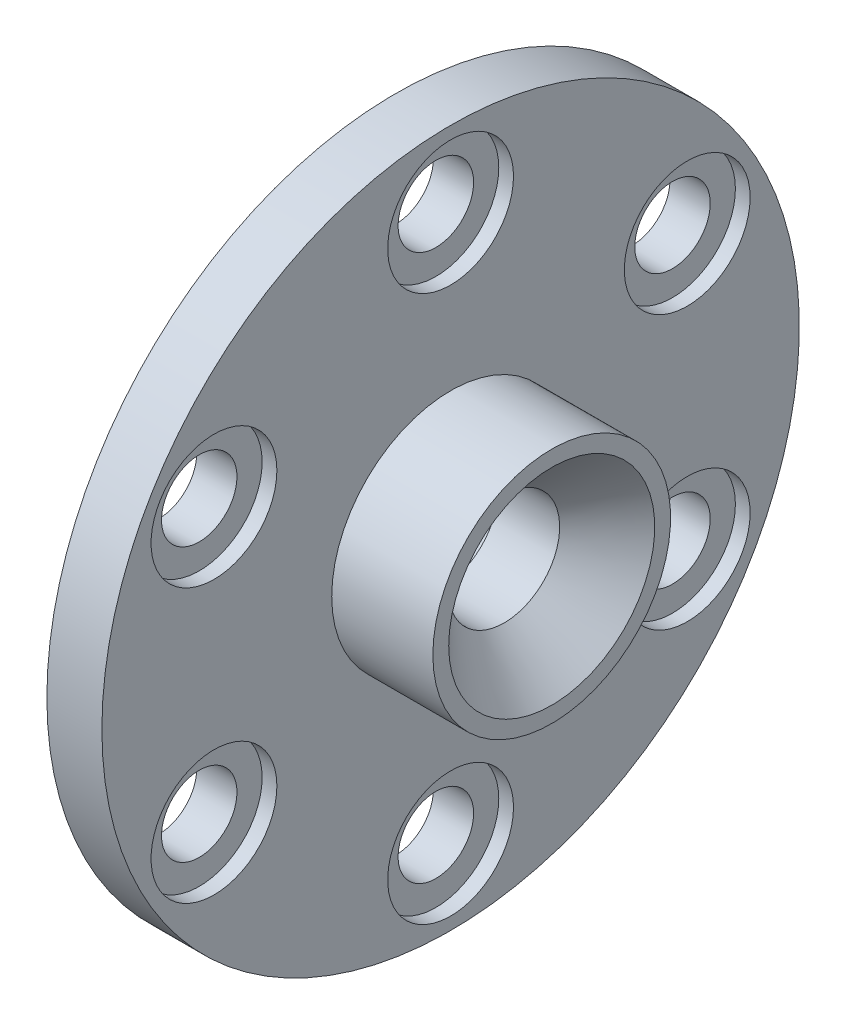
SolidWorks part; units mm, degrees
ref_plane "Front Plane" through (0, 0, 0) normal (0, 0, 1) x (1, 0, 0)
ref_plane "Top Plane" through (0, 0, 0) normal (0, 1, 0) x (1, 0, 0)
ref_plane "Right Plane" through (0, 0, 0) normal (1, 0, 0) x (0, 0, -1)
sketch "Sketch2" plane through (0, 0, 0) normal (0, 0, 1) x (1, 0, 0)
  line L0 (0, 0) -> (58.591, 0) construction
  line L2 (0, 0) -> (18.4, 0)
  line L3 (0, 0) -> (0, 2.5)
  line L4 (0, 2.5) -> (18.4, 2.5)
  line L5 (18.4, 0) -> (18.4, 2.5)
  line L6 (6, 2.5) -> (6, 6)
  line L11 (6, 6) -> (9.97, 6)
  line L16 (12.97, 6) -> (12.97, 3)
  line L17 (12.97, 3) -> (13.6304, 3)
  line L18 (13.6304, 3) -> (13.6304, 2.5)
  line L19 (13.6304, 2.5) -> (6, 2.5)
  line L22 (13.6304, 2.5) -> (16.1104, 2.5)
  line L23 (13.6304, 2.5) -> (13.6304, 4)
  line L24 (13.6304, 4) -> (16.1104, 4)
  line L25 (16.1104, 2.5) -> (16.1104, 4)
  line L27 (6, 6) -> (9.97, 6)
  line L28 (6, 6) -> (6, 9)
  line L29 (6, 9) -> (9.97, 9)
  line L30 (9.97, 6) -> (9.97, 9)
  line L31 (6, 9) -> (6, 8.25)
  line L32 (6, 8.25) -> (5, 8.25)
  line L33 (8.58, 22.001) -> (8.58, 12.476) construction
  line L34 (5, 12.476) -> (12.16, 12.476)
  line L35 (9.97, 9) -> (12.16, 9)
  line L36 (5, 7.5) -> (3, 7.5)
  line L37 (5, 8.25) -> (5, 12.476)
  line L38 (5, 7.5) -> (5, 14)
  line L39 (5, 14) -> (3, 14)
  line L40 (3, 7.5) -> (3, 14)
  line L41 (5, 22.001) -> (12.16, 22.001)
  line L42 (5, 22.001) -> (5, 30.1625)
  line L43 (5, 30.1625) -> (12.16, 30.1625)
  line L44 (12.16, 22.001) -> (12.16, 30.1625)
  line L49 (16.6304, 22.001) -> (16.6304, 7.5)
  line L51 (23.0104, 7.5) -> (23.0104, 6.5)
  line L54 (16.1104, 4) -> (13.6304, 4)
  line L56 (18.0304, 7.5) -> (23.0104, 7.5)
  line L57 (13.16, 22.001) -> (16.6304, 22.001)
  line L58 (16.1104, 3.5) -> (20.0104, 3.5)
  line L59 (29.9004, 14) -> (26.9004, 11)
  line L60 (4, 31.75) -> (18.0304, 31.75)
  line L61 (18.0304, 7.5) -> (23.0104, 7.5)
  line L62 (18.0304, 7.5) -> (18.0304, 12)
  line L63 (18.0304, 12) -> (23.0104, 12)
  line L64 (23.0104, 7.5) -> (23.0104, 12)
  line L65 (18.0304, 31.75) -> (18.0304, 12)
  line L66 (23.0104, 11) -> (26.9004, 11)
  line L67 (34.8004, 23) -> (31.3004, 19.5)
  line L68 (35.8004, 31) -> (38.7904, 33.99)
  line L69 (29.9004, 14) -> (29.9004, 15)
  line L70 (29.9004, 15) -> (22.9304, 15)
  line L71 (22.9304, 15) -> (21.0304, 15)
  line L72 (18.0304, 7.5) -> (16.6304, 7.5)
  line L73 (21.0304, 15) -> (21.0304, 43)
  line L74 (20.0304, 40) -> (10.0704, 40)
  line L75 (10.0704, 40) -> (4, 40)
  line L76 (21.0304, 43) -> (20.0304, 43)
  line L77 (22.9304, 15) -> (29.9004, 15)
  line L78 (22.9304, 15) -> (22.9304, 21)
  line L79 (22.9304, 21) -> (29.9004, 21)
  line L80 (29.9004, 15) -> (29.9004, 21)
  line L81 (10.0704, 40) -> (20.0304, 40)
  line L82 (10.0704, 40) -> (10.0704, 50)
  line L83 (10.0704, 50) -> (20.0304, 50)
  line L84 (20.0304, 40) -> (20.0304, 50)
  line L85 (4, 40) -> (4, 31.75)
  line L86 (12.97, 3) -> (12.97, 2.5)
  line L87 (31.3004, 19.5) -> (29.9004, 19.5)
  line L88 (21.51, 63.5) -> (21.51, 44)
  line L89 (21.51, 63.5) -> (25.9304, 63.5)
  line L90 (25.9304, 63.5) -> (25.9304, 25)
  line L91 (27.8304, 25) -> (25.9304, 25)
  line L92 (10.0704, 48) -> (9, 48)
  line L93 (9, 48) -> (9, 53.476)
  line L94 (9, 53.476) -> (20.0304, 53.476)
  line L95 (20.0304, 53.476) -> (20.0304, 50)
  line L96 (14.5152, 63.001) -> (14.5152, 53.476) construction
  line L97 (9, 63.001) -> (20.0304, 63.001)
  line L98 (9, 63.001) -> (9, 68.2625)
  line L99 (9, 68.2625) -> (20.0304, 68.2625)
  line L100 (20.0304, 63.001) -> (20.0304, 68.2625)
  line L101 (12.97, 6) -> (11.97, 6)
  line L102 (9, 42.5) -> (5, 42.5)
  line L103 (9, 42.5) -> (9, 55)
  line L104 (9, 55) -> (5, 55)
  line L105 (5, 42.5) -> (5, 55)
  line L106 (9.97, 6) -> (10.87, 6)
  line L107 (27.8304, 25) -> (34.8004, 25)
  line L108 (34.8004, 25) -> (34.8004, 23)
  line L109 (0, 0) -> (-2, 0)
  line L110 (0, 0) -> (0, 11)
  line L111 (27.8304, 25) -> (34.8004, 25)
  line L112 (27.8304, 25) -> (27.8304, 32.5)
  line L113 (27.8304, 32.5) -> (34.8004, 32.5)
  line L114 (34.8004, 25) -> (34.8004, 32.5)
  line L115 (35.8004, 31) -> (34.8004, 31)
  line L116 (27.8304, 32.5) -> (27.8304, 64.5)
  line L117 (21.1827, 74.025) -> (6.8477, 74.025)
  line L118 (6.8477, 74.025) -> (6.8477, 76.2)
  line L119 (38.7904, 47.29) -> (30.8304, 55.25)
  line L120 (0, 11) -> (-2, 11)
  line L121 (38.7904, 43.815) -> (30.8529, 43.815)
  line L123 (-4.8, 69.85) -> (1.55, 76.2)
  line L124 (38.7904, 47.29) -> (38.7904, 33.99)
  line L125 (-2, 0) -> (-2, 11)
  line L126 (38.7904, 37.465) -> (30.8529, 37.465)
  line L127 (30.8529, 43.815) -> (30.8529, 37.465)
  line L128 (6, 2.5) -> (6, 0)
  line L129 (0, 63.5) -> (0, 30)
  line L132 (5, 63.5) -> (0, 63.5)
  line L136 (-1.8, 30) -> (-11.76, 30)
  line L138 (-13.76, 25.4) -> (-2, 25.4)
  line L139 (-2, 25.4) -> (-2, 11.5)
  line L140 (27.8304, 64.5) -> (21.1827, 64.5)
  line L141 (-1.8, 30) -> (-11.76, 30)
  line L142 (-1.8, 30) -> (-1.8, 39)
  line L143 (-1.8, 39) -> (-11.76, 39)
  line L144 (-11.76, 30) -> (-11.76, 39)
  line L145 (21.1827, 64.5) -> (21.1827, 74.025)
  line L146 (-12.76, 37) -> (-12.76, 47.29)
  line L147 (-12.76, 37) -> (-11.76, 37)
  line L148 (30.8304, 55.25) -> (30.8304, 76.2)
  line L149 (11.97, 6) -> (11.97, 5.45)
  line L154 (-2, 11.5) -> (1, 11.5)
  line L155 (5, 60.6197) -> (24.05, 60.6197)
  line L160 (5, 60.6197) -> (5, 55.8572)
  line L161 (5, 55.8572) -> (24.05, 55.8572)
  line L166 (24.05, 60.6197) -> (24.05, 55.8572)
  line L167 (5, 60.6197) -> (24.05, 55.8572) construction
  line L172 (5, 55.8572) -> (24.05, 60.6197) construction
  line L173 (24.05, 62.2072) -> (25.9304, 62.2072)
  line L174 (11.97, 5.45) -> (10.87, 5.45)
  line L175 (10.87, 6) -> (10.87, 5.45)
  line L176 (24.05, 62.2072) -> (24.05, 54.2697)
  line L177 (24.05, 54.2697) -> (25.9304, 54.2697)
  line L178 (25.9304, 62.2072) -> (25.9304, 54.2697)
  line L179 (24.05, 62.2072) -> (25.9304, 54.2697) construction
  line L180 (24.05, 54.2697) -> (25.9304, 62.2072) construction
  line L181 (3, 19.6197) -> (15.7, 19.6197)
  line L182 (3, 19.6197) -> (3, 14.8572)
  line L183 (3, 14.8572) -> (15.7, 14.8572)
  line L184 (15.7, 19.6197) -> (15.7, 14.8572)
  line L185 (3, 19.6197) -> (15.7, 14.8572) construction
  line L186 (3, 14.8572) -> (15.7, 19.6197) construction
  line L187 (15.7, 21.2072) -> (16.6304, 21.2072)
  line L188 (15.7, 21.2072) -> (15.7, 13.2697)
  line L189 (15.7, 13.2697) -> (16.6304, 13.2697)
  line L190 (16.6304, 21.2072) -> (16.6304, 13.2697)
  line L191 (15.7, 21.2072) -> (16.6304, 13.2697) construction
  line L192 (15.7, 13.2697) -> (16.6304, 21.2072) construction
  line L193 (1, 11.5) -> (1, 6.5)
  line L194 (1, 6.5) -> (3, 6.5)
  line L195 (23.0104, 6.5) -> (20.0104, 3.5)
  line L196 (5, 63.5) -> (5, 42.5)
  line L197 (5, 42.5) -> (3, 42.5)
  line L198 (3, 42.5) -> (3, 6.5)
  line L199 (6, 0) -> (12.97, 0)
  line L200 (12.97, 0) -> (12.97, 2.5)
  line L201 (18.0304, 31.75) -> (18.0304, 35.875)
  line L202 (18.0304, 35.875) -> (21.0304, 35.875)
  line L203 (30.8304, 76.2) -> (6.8477, 76.2)
  line L204 (3.4027, 69.85) -> (7.8477, 69.85) construction
  line L205 (7.8477, 67.4687) -> (26.8977, 67.4688)
  line L206 (7.8477, 74.025) -> (7.8477, 64.5)
  line L207 (7.8477, 64.5) -> (-1.8, 64.5)
  line L208 (-1.8, 64.5) -> (-1.8, 39)
  line L209 (-12.76, 47.29) -> (-4.8, 55.25)
  line L210 (-4.8, 55.25) -> (-4.8, 69.85)
  line L211 (7.8477, 67.4687) -> (7.8477, 72.2313)
  line L212 (7.8477, 72.2313) -> (26.8977, 72.2313)
  line L213 (26.8977, 67.4688) -> (26.8977, 72.2313)
  line L214 (26.8977, 73.8187) -> (30.8304, 73.8187)
  line L215 (26.8977, 73.8187) -> (26.8977, 65.8813)
  line L216 (26.8977, 65.8813) -> (30.8304, 65.8813)
  line L217 (30.8304, 73.8187) -> (30.8304, 65.8813)
  line L218 (3.4027, 72.2313) -> (25.6277, 72.2313)
  line L219 (3.4027, 72.2313) -> (3.4027, 67.4687)
  line L220 (3.4027, 67.4687) -> (25.6277, 67.4687)
  line L221 (25.6277, 72.2313) -> (25.6277, 67.4687)
  line L222 (25.6277, 69.85) -> (21.1827, 69.85) construction
  line L223 (21.51, 44) -> (22.9304, 44)
  line L224 (22.9304, 44) -> (22.9304, 21)
  line L225 (13.6304, 4) -> (13.6304, 12.2697)
  line L226 (13.6304, 12.2697) -> (13.16, 12.2697)
  line L227 (13.16, 12.2697) -> (13.16, 22.001)
  line L228 (12.16, 9) -> (12.16, 12.476)
  line L229 (-1.8, 30) -> (0, 30)
  line L230 (9, 65.6317) -> (3.4027, 65.6317) construction
  line L231 (20.0304, 65.6317) -> (25.6277, 65.6317) construction
  line L232 (1.55, 76.2) -> (6.8477, 76.2)
  line L233 (-11.76, 30) -> (-13.76, 30)
  line L234 (-13.76, 30) -> (-13.76, 25.4)
  circle A0 centre (26.8804, 25.95) radius 0.95
  circle A1 centre (21.9804, 15.95) radius 0.95
  circle A2 centre (17.3304, 8.2) radius 0.7
  circle A3 centre (10.42, 6.45) radius 0.45
  circle A4 centre (-0.9, 30.9) radius 0.9
  point P7 (24.9902, 58.2385)
  point P131 (16.1652, 17.2385)
  point P135 (14.525, 58.2385)
  point P146 (9.35, 17.2385)
sketch "Sketch3" plane through (0, 0, 0) normal (0, 0, 1) x (1, 0, 0)
  line L0 (13.16, 22.001) -> (16.6304, 22.001) construction
  line L1 (16.6304, 22.001) -> (16.6304, 7.5) construction
  line L4 (23.0104, 7.5) -> (23.0104, 6.5) construction
  line L5 (18.0304, 7.5) -> (23.0104, 7.5) construction
  line L7 (13.6304, 4) -> (16.1104, 4) construction
  line L8 (16.1104, 2.5) -> (16.1104, 4) construction
  line L9 (16.1104, 3.5) -> (20.0104, 3.5) construction
  line L10 (23.0104, 6.5) -> (20.0104, 3.5) construction
  line L11 (13.16, 22.001) -> (16.6304, 22.001)
  line L12 (16.6304, 22.001) -> (16.6304, 7.5)
  line L15 (23.0104, 7.5) -> (23.0104, 6.5)
  line L16 (18.0304, 7.5) -> (23.0104, 7.5)
  line L18 (13.6304, 4) -> (16.1104, 4)
  line L19 (16.1104, 3.5) -> (16.1104, 4)
  line L20 (16.1104, 3.5) -> (20.0104, 3.5)
  line L21 (23.0104, 6.5) -> (20.0104, 3.5)
  line L22 (18.0304, 7.5) -> (16.6304, 7.5) construction
  line L23 (13.6304, 4) -> (13.6304, 12.2697) construction
  line L24 (13.6304, 12.2697) -> (13.16, 12.2697) construction
  line L25 (13.16, 12.2697) -> (13.16, 22.001) construction
  line L26 (18.0304, 7.5) -> (16.6304, 7.5)
  line L27 (13.6304, 4) -> (13.6304, 12.2697)
  line L28 (13.6304, 12.2697) -> (13.16, 12.2697)
  line L29 (13.16, 12.2697) -> (13.16, 22.001)
revolve "Revolve1" add sketch "Sketch3" angle 360 about L0
sketch "Sketch4" plane through (0, 0, 0) normal (1, 0, 0) x (0, 0, -1)
  line L0 (0, 0) -> (0, 69.85) construction
  line L1 (0, 0) -> (13.6271, 68.5079) construction
  line L2 (0, 0) -> (0, 58.2385) construction
  line L3 (0, 0) -> (50.436, 29.1192) construction
  line L4 (0, 0) -> (0, 31.75) construction
  line L5 (0, 0) -> (12.1502, 29.3332) construction
  line L6 (0, 0) -> (0, 17.2385) construction
  line L7 (0, 0) -> (14.929, 8.6192) construction
  line L8 (0, 0) -> (0, 58.2385) construction
  line L9 (0, 0) -> (50.436, 29.1192) construction
  line L10 (0, 0) -> (5.9583, 29.9542) construction
  line L11 (0, 0) -> (16.9677, 25.394) construction
  circle A0 centre (0, 0) radius 69.85 construction
  circle A1 centre (0, 0) radius 58.2385 construction
  circle A2 centre (0, 0) radius 31.75 construction
  circle A3 centre (0, 0) radius 17.2385 construction
  circle A4 centre (0, 69.85) radius 3.175
  circle A5 centre (0, 58.2385) radius 4.7625
  circle A6 centre (0, 31.75) radius 3.175
  circle A7 centre (0, 17.2385) radius 4.7625
  circle A8 centre (13.6271, 68.5079) radius 3.175
  circle A9 centre (26.7304, 64.533) radius 3.175
  circle A10 centre (38.8066, 58.0782) radius 3.175
  circle A11 centre (49.3914, 49.3914) radius 3.175
  circle A12 centre (58.0782, 38.8066) radius 3.175
  circle A13 centre (64.533, 26.7304) radius 3.175
  circle A14 centre (68.5079, 13.6271) radius 3.175
  circle A15 centre (69.85, 0) radius 3.175
  circle A16 centre (68.5079, -13.6271) radius 3.175
  circle A17 centre (64.533, -26.7304) radius 3.175
  circle A18 centre (58.0782, -38.8066) radius 3.175
  circle A19 centre (49.3914, -49.3914) radius 3.175
  circle A20 centre (38.8066, -58.0782) radius 3.175
  circle A21 centre (26.7304, -64.533) radius 3.175
  circle A22 centre (13.6271, -68.5079) radius 3.175
  circle A23 centre (0, -69.85) radius 3.175
  circle A24 centre (-13.6271, -68.5079) radius 3.175
  circle A25 centre (-26.7304, -64.533) radius 3.175
  circle A26 centre (-38.8066, -58.0782) radius 3.175
  circle A27 centre (-49.3914, -49.3914) radius 3.175
  circle A28 centre (-58.0782, -38.8066) radius 3.175
  circle A29 centre (-64.533, -26.7304) radius 3.175
  circle A30 centre (-68.5079, -13.6271) radius 3.175
  circle A31 centre (-69.85, 0) radius 3.175
  circle A32 centre (-68.5079, 13.6271) radius 3.175
  circle A33 centre (-64.533, 26.7304) radius 3.175
  circle A34 centre (-58.0782, 38.8066) radius 3.175
  circle A35 centre (-49.3914, 49.3914) radius 3.175
  circle A36 centre (-38.8066, 58.0782) radius 3.175
  circle A37 centre (-26.7304, 64.533) radius 3.175
  circle A38 centre (-13.6271, 68.5079) radius 3.175
  circle A47 centre (50.436, 29.1192) radius 4.7625
  circle A48 centre (50.436, -29.1192) radius 4.7625
  circle A49 centre (0, -58.2385) radius 4.7625
  circle A50 centre (-50.436, -29.1192) radius 4.7625
  circle A51 centre (-50.436, 29.1192) radius 4.7625
  circle A58 centre (12.1502, 29.3332) radius 3.175
  circle A59 centre (22.4506, 22.4506) radius 3.175
  circle A60 centre (29.3332, 12.1502) radius 3.175
  circle A61 centre (31.75, 0) radius 3.175
  circle A62 centre (29.3332, -12.1502) radius 3.175
  circle A63 centre (22.4506, -22.4506) radius 3.175
  circle A64 centre (12.1502, -29.3332) radius 3.175
  circle A65 centre (0, -31.75) radius 3.175
  circle A66 centre (-12.1502, -29.3332) radius 3.175
  circle A67 centre (-22.4506, -22.4506) radius 3.175
  circle A68 centre (-29.3332, -12.1502) radius 3.175
  circle A69 centre (-31.75, 0) radius 3.175
  circle A70 centre (-29.3332, 12.1502) radius 3.175
  circle A71 centre (-22.4506, 22.4506) radius 3.175
  circle A72 centre (14.929, 8.6192) radius 4.7625
  circle A73 centre (14.929, -8.6192) radius 4.7625
  circle A74 centre (0, -17.2385) radius 4.7625
  circle A75 centre (-14.929, -8.6192) radius 4.7625
  circle A76 centre (-14.929, 8.6192) radius 4.7625
  circle A77 centre (0, 0) radius 50
  circle A78 centre (0, 0) radius 9
  circle A79 centre (-12.1502, 29.3332) radius 3.175
  circle A80 centre (0, 0) radius 76.2
  circle A81 centre (0, 0) radius 74.025
  circle A82 centre (0, 69.85) radius 3.9687
  circle A83 centre (49.3914, 49.3914) radius 3.9687
  circle A84 centre (69.85, 0) radius 3.9688
  circle A85 centre (49.3914, -49.3914) radius 3.9687
  circle A86 centre (0, -69.85) radius 3.9687
  circle A87 centre (-49.3914, -49.3914) radius 3.9687
  circle A88 centre (-69.85, 0) radius 3.9688
  circle A89 centre (-49.3914, 49.3914) radius 3.9687
  circle A90 centre (0, 69.85) radius 2.3812
  circle A91 centre (13.6271, 68.5079) radius 2.3812
  circle A92 centre (26.7304, 64.533) radius 2.3813
  circle A93 centre (38.8066, 58.0782) radius 2.3812
  circle A94 centre (49.3914, 49.3914) radius 2.3812
  circle A95 centre (58.0782, 38.8066) radius 2.3812
  circle A96 centre (64.533, 26.7304) radius 2.3813
  circle A97 centre (68.5079, 13.6271) radius 2.3813
  circle A98 centre (69.85, 0) radius 2.3813
  circle A99 centre (68.5079, -13.6271) radius 2.3813
  circle A100 centre (64.533, -26.7304) radius 2.3813
  circle A101 centre (58.0782, -38.8066) radius 2.3812
  circle A102 centre (49.3914, -49.3914) radius 2.3812
  circle A103 centre (38.8066, -58.0782) radius 2.3812
  circle A104 centre (26.7304, -64.533) radius 2.3813
  circle A105 centre (13.6271, -68.5079) radius 2.3812
  circle A106 centre (0, -69.85) radius 2.3812
  circle A107 centre (-13.6271, -68.5079) radius 2.3812
  circle A108 centre (-26.7304, -64.533) radius 2.3813
  circle A109 centre (-38.8066, -58.0782) radius 2.3812
  circle A110 centre (-49.3914, -49.3914) radius 2.3812
  circle A111 centre (-58.0782, -38.8066) radius 2.3812
  circle A112 centre (-64.533, -26.7304) radius 2.3812
  arc A113 (3.0399, 30.8338) -> (8.9911, 29.65) centre (5.9583, 29.9542) cw
  arc A114 (14.6081, 27.3234) -> (19.6532, 23.9523) centre (16.9677, 25.394) cw
  arc A115 (23.9523, 19.6532) -> (27.3234, 14.6081) centre (25.394, 16.9677) cw
  arc A116 (29.65, 8.9911) -> (30.8338, 3.0399) centre (29.9542, 5.9583) cw
  arc A117 (30.8338, -3.0399) -> (29.65, -8.9911) centre (29.9542, -5.9583) cw
  arc A118 (27.3234, -14.6081) -> (23.9523, -19.6532) centre (25.394, -16.9677) cw
  arc A119 (19.6532, -23.9523) -> (14.6081, -27.3234) centre (16.9677, -25.394) cw
  arc A120 (8.9911, -29.65) -> (3.0399, -30.8338) centre (5.9583, -29.9542) cw
  arc A121 (-3.0399, -30.8338) -> (-8.9911, -29.65) centre (-5.9583, -29.9542) cw
  arc A122 (-14.6081, -27.3234) -> (-19.6532, -23.9523) centre (-16.9677, -25.394) cw
  arc A123 (-23.9523, -19.6532) -> (-27.3234, -14.6081) centre (-25.394, -16.9677) cw
  arc A124 (-29.65, -8.9911) -> (-30.8338, -3.0399) centre (-29.9542, -5.9583) cw
  arc A125 (-30.8338, 3.0399) -> (-29.65, 8.9911) centre (-29.9542, 5.9583) cw
  arc A126 (-27.3234, 14.6081) -> (-23.9523, 19.6532) centre (-25.394, 16.9677) cw
  arc A127 (-19.6532, 23.9523) -> (-14.6081, 27.3234) centre (-16.9677, 25.394) cw
  arc A128 (-8.9911, 29.65) -> (-3.0399, 30.8338) centre (-5.9583, 29.9542) cw
  arc A129 (26.9875, 0) -> (26.9932, 0.1932) centre (30.2705, 0) cw
  arc A130 (65.0988, 0.2771) -> (65.0875, 0) centre (68.4964, 0) ccw
  circle A131 centre (1.5875, 0) radius 40
  circle A132 centre (1.5875, 0) radius 2.5
  circle A133 centre (1.5875, 0) radius 3
  circle A134 centre (1.5875, 0) radius 43
  circle A135 centre (-68.5079, -13.6271) radius 2.3813
  circle A136 centre (-69.85, 0) radius 2.3813
  circle A137 centre (-68.5079, 13.6271) radius 2.3813
  circle A138 centre (-64.533, 26.7304) radius 2.3812
  circle A139 centre (-58.0782, 38.8066) radius 2.3812
  circle A140 centre (-49.3914, 49.3914) radius 2.3812
  circle A141 centre (-38.8066, 58.0782) radius 2.3812
  circle A142 centre (-26.7304, 64.533) radius 2.3813
  circle A143 centre (-13.6271, 68.5079) radius 2.3812
  circle A144 centre (0, 58.2385) radius 2.3812
  circle A145 centre (0, 58.2385) radius 3.9688
  circle A146 centre (50.436, 29.1192) radius 3.9688
  circle A147 centre (50.436, 29.1192) radius 2.3813
  circle A148 centre (50.436, -29.1192) radius 3.9687
  circle A149 centre (50.436, -29.1192) radius 2.3812
  circle A150 centre (0, -58.2385) radius 3.9687
  circle A151 centre (0, -58.2385) radius 2.3812
  circle A152 centre (-50.436, -29.1192) radius 3.9687
  circle A153 centre (-50.436, -29.1192) radius 2.3812
  circle A154 centre (-50.436, 29.1192) radius 3.9687
  circle A155 centre (-50.436, 29.1192) radius 2.3812
  spline S1 degree 4 poles (26.9875, 0) (26.9875, -0.0248) (26.9882, -0.0743) (26.9912, -0.1613) (26.9992, -0.2849) (27.0142, -0.4323) (27.0403, -0.5994) (27.0821, -0.7965) (27.1455, -1.0177) (27.2241, -1.2336) (27.3173, -1.4437) (27.4329, -1.6623) (27.5739, -1.8864) (27.7427, -2.1125) (27.9417, -2.3365) (28.1305, -2.5184) (28.3007, -2.6647) (28.4457, -2.7828) (28.5617, -2.8775) (28.6745, -2.9758) (28.7813, -3.0807) (28.9057, -3.2206) (29.0482, -3.4108) (29.197, -3.6576) (29.3758, -4.0447) (29.5291, -4.5502) (29.6152, -5.1612) (29.5933, -5.8758) (29.4507, -6.5869) (29.186, -7.2733) (28.8461, -7.831) (28.4818, -8.2549) (28.1375, -8.5536) (27.8792, -8.7284) (27.6484, -8.8496) (27.4154, -8.9438) (27.2144, -9.0029) (27.0118, -9.0554) (26.7709, -9.1263) (26.5334, -9.2082) (26.2634, -9.3231) (25.9685, -9.4827) (25.5538, -9.7623) (25.0678, -10.2216) (24.6281, -10.8948) (24.3613, -11.7878) (24.3459, -12.6097) (24.4764, -13.2366) (24.6525, -13.7006) (24.8058, -14.0202) (24.9382, -14.271) (25.0503, -14.5321) (25.1258, -14.8064) (25.1736, -15.0995) (25.1911, -15.4094) (25.1742, -15.8163) (25.0891, -16.3148) (24.907, -16.8764) (24.5182, -17.6315) (23.9757, -18.2942) (23.3695, -18.7764) (22.7564, -19.084) (22.3641, -19.2199) (22.0554, -19.2923) (21.7533, -19.3289) (21.4612, -19.3296) (21.1723, -19.2896) (20.8852, -19.2417) (20.5956, -19.2104) (20.3043, -19.1994) (19.8669, -19.2177) (19.2899, -19.3231) (18.5833, -19.6092) (17.8444, -20.1834) (17.3807, -20.828) (17.1316, -21.424) (17.0182, -21.8879) (16.9714, -22.1971) (16.9537, -22.4701) (16.9533, -22.7044) (16.9619, -22.9384) (16.9737, -23.1333) (16.977, -23.3286) (16.9594, -23.5624) (16.9177, -23.8101) (16.834, -24.1055) (16.6578, -24.5276) (16.3623, -25.0151) (15.9278, -25.5198) (15.3432, -25.99) (14.6957, -26.3472) (14.0068, -26.5857) (13.3856, -26.6851) (12.847, -26.6849) (12.4166, -26.6224) (12.1324, -26.5468) (11.9058, -26.4598) (11.7342, -26.3753) (11.6017, -26.2989) (11.4727, -26.2169) (11.3444, -26.1337) (11.1825, -26.0322) (10.9836, -25.9179) (10.7435, -25.7991) (10.4587, -25.6867) (10.0106, -25.5536) (9.3843, -25.468) (8.599, -25.5363) (7.7243, -25.8773) (7.1093, -26.3459) (6.716, -26.8042) (6.4745, -27.1841) (6.3352, -27.4489) (6.215, -27.7227) (6.1113, -28.0028) (5.9959, -28.2789) (5.841, -28.5357) (5.6522, -28.7792) (5.4316, -29.007) (5.1188, -29.2711) (4.6965, -29.5439) (4.1624, -29.7882) (3.5487, -29.9564) (2.9521, -30.0296) (2.386, -30.0225) (1.8595, -29.949) (1.3409, -29.8055) (0.9058, -29.6147) (0.5544, -29.4004) (0.2828, -29.1832) (0.0847, -28.9875) (-0.0865, -28.768) (-0.2353, -28.5332) (-0.3904, -28.3016) (-0.5598, -28.0786) (-0.792, -27.8146) (-1.1036, -27.5274) (-1.5105, -27.2448) (-2.0688, -26.9834) (-2.7167, -26.8202) (-3.459, -26.7949) (-4.1529, -26.9407) (-4.7224, -27.1899) (-5.1296, -27.455) (-5.3866, -27.661) (-5.5925, -27.8507) (-5.7558, -28.014) (-5.9199, -28.1766) (-6.0977, -28.3246) (-6.3382, -28.4851) (-6.6906, -28.6628) (-7.1669, -28.8182) (-7.7668, -28.9076) (-8.4201, -28.8957) (-9.0747, -28.7804) (-9.7144, -28.5614) (-10.3217, -28.2381) (-10.8061, -27.8636) (-11.1671, -27.4837) (-11.4143, -27.1402) (-11.5734, -26.859) (-11.6946, -26.573) (-11.7735, -26.2857) (-11.8173, -25.9915) (-11.8668, -25.6988) (-11.9353, -25.4093) (-12.0257, -25.1261) (-12.198, -24.7091) (-12.5089, -24.187) (-13.0379, -23.6191) (-13.8448, -23.1355) (-14.6072, -22.9365) (-15.2369, -22.9149) (-15.701, -22.9694) (-16.0024, -23.0316) (-16.2609, -23.107) (-16.4782, -23.1841) (-16.6576, -23.2529) (-16.8015, -23.307) (-16.9839, -23.3672) (-17.2087, -23.4203) (-17.4853, -23.4534) (-17.811, -23.4543) (-18.2291, -23.4104) (-18.7305, -23.2885) (-19.2884, -23.06) (-19.8603, -22.7052) (-20.3581, -22.2764) (-20.7758, -21.7899) (-21.1086, -21.2598) (-21.3336, -20.7318) (-21.4619, -20.2263) (-21.5006, -19.8113) (-21.4889, -19.4989) (-21.4468, -19.2424) (-21.3965, -19.0408) (-21.34, -18.8332) (-21.2878, -18.6168) (-21.2341, -18.3322) (-21.1962, -17.9773) (-21.1985, -17.5604) (-21.2781, -17.0173) (-21.4721, -16.4256) (-21.838, -15.7861) (-22.3482, -15.2578) (-22.8946, -14.8957) (-23.3828, -14.6878) (-23.7368, -14.5834) (-24.0536, -14.5215) (-24.3285, -14.4876) (-24.6045, -14.47) (-24.8811, -14.458) (-25.1556, -14.4184) (-25.4228, -14.3439) (-25.6932, -14.2375) (-26.1109, -14.0218) (-26.5677, -13.6822) (-27.0258, -13.1981) (-27.4314, -12.5682) (-27.7017, -11.9578) (-27.8746, -11.3112) (-27.9332, -10.727) (-27.9111, -10.2247) (-27.8415, -9.8214) (-27.7568, -9.5159) (-27.6427, -9.2298) (-27.5004, -8.9659) (-27.3212, -8.7261) (-27.1301, -8.4966) (-26.9071, -8.1967) (-26.6417, -7.7583) (-26.3997, -7.1508) (-26.2841, -6.3875) (-26.3642, -5.5798) (-26.6019, -4.9055) (-26.9193, -4.3761) (-27.2736, -3.9636) (-27.583, -3.6904) (-27.8719, -3.4871) (-28.1186, -3.3407) (-28.3135, -3.2371) (-28.5043, -3.1411) (-28.6854, -3.0419) (-28.9002, -2.8984) (-29.1355, -2.6958) (-29.4123, -2.3882) (-29.6958, -1.9552) (-29.932, -1.437) (-30.0985, -0.839) (-30.1779, -0.2025) (-30.1603, 0.4599) (-30.0348, 1.1323) (-29.8199, 1.711) (-29.5617, 2.1719) (-29.3035, 2.5118) (-29.0784, 2.748) (-28.8655, 2.924) (-28.6761, 3.0468) (-28.5112, 3.1367) (-28.3775, 3.205) (-28.2106, 3.2911) (-28.0136, 3.4005) (-27.7912, 3.5413) (-27.5508, 3.7219) (-27.2011, 4.0343) (-26.7941, 4.5285) (-26.4419, 5.234) (-26.2777, 6.1494) (-26.351, 6.9081) (-26.5268, 7.4739) (-26.7218, 7.8823) (-26.8619, 8.1196) (-26.9953, 8.3144) (-27.1373, 8.5028) (-27.2613, 8.6553) (-27.3845, 8.8088) (-27.518, 9.0035) (-27.6324, 9.2103) (-27.7412, 9.4693) (-27.8326, 9.7814) (-27.9074, 10.1885) (-27.9345, 10.6913) (-27.8808, 11.2771) (-27.6878, 12.0229) (-27.3166, 12.8111) (-26.8405, 13.4278) (-26.3243, 13.8718) (-25.9118, 14.1263) (-25.6503, 14.2566) (-25.3769, 14.3596) (-25.0933, 14.4318) (-24.8027, 14.4634) (-24.5112, 14.4738) (-24.1629, 14.5033) (-23.7608, 14.5717) (-23.1887, 14.7443) (-22.5511, 15.0901) (-21.962, 15.6231) (-21.544, 16.2749) (-21.3217, 16.857) (-21.2175, 17.3851) (-21.1902, 17.8397) (-21.2185, 18.2374) (-21.2771, 18.5739) (-21.3443, 18.8506) (-21.405, 19.0706) (-21.4579, 19.2928) (-21.4883, 19.5194) (-21.4981, 19.805) (-21.4664, 20.1907) (-21.3565, 20.6672) (-21.1331, 21.2135) (-20.8025, 21.7541) (-20.3882, 22.2461) (-19.8974, 22.677) (-19.3379, 23.033) (-18.7964, 23.2649) (-18.309, 23.3941) (-17.8981, 23.4483) (-17.5726, 23.4572) (-17.2924, 23.4331) (-17.0602, 23.3874) (-16.8337, 23.3199) (-16.6495, 23.2499) (-16.4659, 23.1791) (-16.2424, 23.1025) (-16.0156, 23.0362) (-15.7461, 22.9768) (-15.2967, 22.9185) (-14.7035, 22.9278) (-13.9592, 23.0948) (-13.1407, 23.5365) (-12.5805, 24.0908) (-12.2382, 24.6309) (-12.0505, 25.0599) (-11.9538, 25.3442) (-11.8892, 25.5989) (-11.8463, 25.8198) (-11.8162, 26.0048) (-11.7926, 26.153) (-11.7577, 26.3372) (-11.6989, 26.5548) (-11.5969, 26.8111) (-11.4414, 27.0975) (-11.1977, 27.4473) (-10.8392, 27.8343) (-10.3554, 28.2166) (-9.7549, 28.5431) (-9.1303, 28.7642) (-8.5, 28.8851) (-7.879, 28.911) (-7.3126, 28.8458) (-6.8128, 28.7091) (-6.4345, 28.54) (-6.1692, 28.378) (-5.9665, 28.2173) (-5.8163, 28.0752) (-5.6659, 27.9232) (-5.5067, 27.7699) (-5.2907, 27.5806) (-5.0072, 27.369) (-4.6509, 27.1597) (-4.148, 26.9513) (-3.5452, 26.8146) (-2.8302, 26.7991) (-2.0381, 26.9749) (-1.3495, 27.3225) (-0.8483, 27.741) (-0.5146, 28.1291) (-0.2991, 28.4338) (-0.1401, 28.6862) (0.0331, 28.93) (0.2405, 29.146) (0.4774, 29.3422) (0.7418, 29.5165) (1.1036, 29.7066) (1.5741, 29.882) (2.1471, 30.006) (2.8151, 30.041) (3.4791, 29.9721) (4.2039, 29.7804) (4.8064, 29.4933) (5.2708, 29.1628) (5.6049, 28.8311) (5.7894, 28.6062) (5.9424, 28.3744) (6.0642, 28.1249) (6.161, 27.8653) (6.2635, 27.608) (6.3813, 27.357) (6.5388, 27.0748) (6.7484, 26.7704) (7.0986, 26.3707) (7.6135, 25.9641) (8.2747, 25.644) (8.9962, 25.4959) (9.6181, 25.496) (10.1582, 25.5894) (10.5546, 25.7168) (10.8796, 25.8629) (11.1331, 26.0022) (11.3224, 26.1188) (11.5021, 26.2366) (11.6784, 26.3463) (11.9094, 26.4649) (12.2028, 26.5718) (12.6092, 26.6624) (13.1291, 26.6958) (13.7, 26.6444) (14.3062, 26.4914) (14.8974, 26.2443) (15.459, 25.9029) (15.9732, 25.4681) (16.3631, 25.0071) (16.6337, 24.567) (16.8044, 24.1822) (16.9036, 23.8716) (16.9571, 23.5978) (16.9755, 23.3672) (16.9741, 23.1748) (16.9669, 23.0211) (16.9571, 22.8289) (16.9512, 22.5982) (16.9599, 22.3287) (16.9946, 22.0224) (17.0874, 21.5638) (17.3043, 20.9714) (17.7315, 20.3087) (18.4426, 19.693) (19.1468, 19.3677) (19.739, 19.2351) (20.1882, 19.2012) (20.4852, 19.2034) (20.7812, 19.2282) (21.0745, 19.2719) (21.3675, 19.3208) (21.6648, 19.3336) (21.9737, 19.306) (22.2899, 19.241) (22.6922, 19.1116) (23.1641, 18.8854) (23.669, 18.5404) (24.1634, 18.0628) (24.569, 17.5219) (24.8807, 16.9345) (25.0937, 16.316) (25.184, 15.7743) (25.1924, 15.3317) (25.1581, 14.9969) (25.1154, 14.7695) (25.0522, 14.5468) (24.9658, 14.3321) (24.8616, 14.1257) (24.7568, 13.9198) (24.6402, 13.6649) (24.524, 13.3562) (24.3985, 12.886) (24.3389, 12.2663) (24.4166, 11.5605) (24.6979, 10.7931) (25.0952, 10.2042) (25.5426, 9.7706) (25.9551, 9.4883) (26.2689, 9.3208) (26.5627, 9.1971) (26.83, 9.1062) (27.1019, 9.0315) (27.3749, 8.9598) (27.6385, 8.8574) (27.887, 8.7225) (28.1969, 8.5098) (28.5449, 8.1936) (28.9002, 7.7549) (29.2229, 7.1817) (29.4529, 6.562) (29.5858, 5.9108) (29.6165, 5.2432) (29.5485, 4.659) (29.4188, 4.1725) (29.2636, 3.7931) (29.1144, 3.5129) (28.9404, 3.2582) (28.7432, 3.0317) (28.5155, 2.8371) (28.281, 2.6515) (28.0578, 2.4519) (27.8492, 2.2371) (27.6347, 1.9761) (27.4574, 1.7102) (27.3152, 1.4444) (27.2047, 1.1845) (27.1307, 0.9703) (27.0789, 0.7793) (27.0441, 0.6164) (27.021, 0.472) (27.0061, 0.351) (26.9981, 0.2662) (26.9946, 0.2176) (26.9932, 0.1932) knots 0.06864 0.06864 0.06864 0.06864 0.06864 0.069106 0.069571 0.070037 0.070502 0.071433 0.072364 0.073295 0.074226 0.075157 0.076088 0.077301 0.078514 0.079727 0.08094 0.081547 0.082153 0.08276 0.083366 0.083973 0.084579 0.085792 0.087214 0.088636 0.091479 0.094323 0.097166 0.100174 0.103182 0.10619 0.107694 0.109198 0.110555 0.111234 0.111912 0.113269 0.113948 0.114626 0.115983 0.11734 0.118697 0.120055 0.12408 0.128106 0.131537 0.134967 0.137266 0.138415 0.139565 0.140714 0.141863 0.143013 0.144162 0.145524 0.146885 0.149608 0.152331 0.155054 0.160594 0.163364 0.164749 0.166134 0.167314 0.168495 0.169675 0.170855 0.172035 0.173215 0.174395 0.175575 0.179125 0.182676 0.186612 0.190548 0.191813 0.193079 0.194345 0.195611 0.196244 0.196877 0.198142 0.198775 0.199408 0.200674 0.202207 0.203741 0.206808 0.209874 0.212941 0.21584 0.218738 0.221637 0.223086 0.224535 0.225775 0.226394 0.227014 0.227634 0.228253 0.228873 0.229493 0.230732 0.231971 0.233211 0.23445 0.238303 0.242155 0.245814 0.249472 0.250683 0.251894 0.253105 0.254316 0.255527 0.256738 0.257949 0.25916 0.260514 0.261868 0.264577 0.267285 0.269993 0.272142 0.27429 0.276439 0.278588 0.280839 0.281965 0.283091 0.284217 0.285343 0.286469 0.287595 0.288737 0.289879 0.292163 0.294447 0.296732 0.299827 0.302922 0.306383 0.308113 0.309844 0.31078 0.311716 0.312652 0.313588 0.314524 0.31546 0.317332 0.319969 0.322606 0.325244 0.327881 0.330703 0.333524 0.336346 0.337757 0.339168 0.340372 0.341576 0.34278 0.343984 0.345188 0.346392 0.347596 0.3488 0.352495 0.356189 0.36002 0.36385 0.365096 0.366342 0.367588 0.368834 0.369457 0.370079 0.370702 0.371325 0.372571 0.373817 0.375207 0.376596 0.379375 0.382154 0.384933 0.387459 0.389986 0.392513 0.39504 0.396723 0.398407 0.399249 0.400091 0.400932 0.401774 0.402737 0.4037 0.405625 0.407551 0.409476 0.412569 0.415662 0.41939 0.421254 0.423119 0.42424 0.425361 0.426483 0.427604 0.428726 0.429847 0.430969 0.43209 0.433431 0.437455 0.440138 0.44282 0.445528 0.448236 0.450943 0.452297 0.453651 0.454862 0.456073 0.457284 0.458495 0.459706 0.460916 0.463338 0.466783 0.470228 0.473297 0.476366 0.478273 0.480179 0.482085 0.483038 0.483991 0.484828 0.485664 0.486501 0.487337 0.48901 0.490683 0.493189 0.495695 0.498202 0.500708 0.503552 0.506397 0.509241 0.510663 0.512085 0.513303 0.514521 0.51513 0.515738 0.516347 0.516956 0.518174 0.519391 0.520609 0.521827 0.525766 0.529706 0.533208 0.53671 0.537985 0.53926 0.540535 0.541173 0.54181 0.543085 0.543723 0.54436 0.545635 0.54691 0.548267 0.549623 0.552335 0.555047 0.55776 0.562061 0.566363 0.567545 0.568728 0.56991 0.571092 0.572275 0.573457 0.574639 0.575822 0.577939 0.580057 0.584292 0.587472 0.590653 0.592493 0.594334 0.596174 0.598014 0.59894 0.599865 0.60079 0.601715 0.60264 0.603565 0.605415 0.607973 0.610531 0.61309 0.615648 0.618364 0.62108 0.623796 0.625154 0.626512 0.627788 0.629065 0.629703 0.630341 0.631618 0.632256 0.632895 0.634171 0.635448 0.636724 0.640232 0.643739 0.647674 0.651609 0.652825 0.65404 0.655256 0.656472 0.65708 0.657688 0.658296 0.658904 0.66012 0.661336 0.662756 0.664177 0.667018 0.669858 0.672699 0.675209 0.677718 0.680227 0.682736 0.684412 0.686087 0.686924 0.687762 0.688599 0.689437 0.690391 0.691345 0.693254 0.695162 0.697071 0.700143 0.703216 0.706655 0.710095 0.712514 0.713723 0.714933 0.716142 0.717352 0.718561 0.719771 0.721123 0.722475 0.725179 0.727883 0.730587 0.733273 0.735959 0.739989 0.741332 0.742455 0.743577 0.7447 0.745823 0.746945 0.748068 0.749191 0.750314 0.752181 0.754048 0.757782 0.760871 0.763961 0.765883 0.767806 0.769729 0.77069 0.771651 0.772492 0.773333 0.774174 0.775015 0.776698 0.77838 0.780903 0.783427 0.785951 0.788475 0.791257 0.794039 0.796822 0.798213 0.799604 0.800852 0.802099 0.802723 0.803347 0.803971 0.804595 0.805842 0.80709 0.808337 0.809585 0.81342 0.817255 0.820945 0.824634 0.825837 0.827039 0.828242 0.829444 0.830647 0.831849 0.833052 0.834254 0.835663 0.837072 0.83989 0.842708 0.845526 0.848167 0.850807 0.853447 0.856087 0.857024 0.857961 0.858897 0.859834 0.860771 0.861707 0.862644 0.863581 0.865314 0.867048 0.870515 0.873613 0.876711 0.880181 0.881916 0.883651 0.884794 0.885937 0.887081 0.888224 0.889367 0.89051 0.891653 0.892797 0.895451 0.898105 0.90076 0.903414 0.906126 0.908838 0.911549 0.912905 0.914261 0.915474 0.916686 0.917899 0.919111 0.920323 0.921536 0.922748 0.923961 0.925793 0.926709 0.927625 0.928541 0.929457 0.929915 0.930373 0.930831 0.931289 0.931289 0.931289 0.931289 0.931289
  spline S3 degree 4 poles (65.0875, 0) (65.0875, -0.2085) (65.1336, -0.6093) (65.3196, -1.4523) (65.739, -2.0447) (66.242, -2.6341) (66.7299, -3.0916) (67.1731, -3.6257) (67.5219, -4.2566) (67.8399, -5.1354) (68.0042, -6.2629) (67.9043, -7.3956) (67.5534, -8.464) (67.1166, -9.2437) (66.7001, -9.7852) (66.2223, -10.2316) (65.7042, -10.5824) (65.1033, -10.9671) (64.5015, -11.4984) (63.9836, -12.2541) (63.7076, -13.0981) (63.6577, -13.8665) (63.7509, -14.5541) (63.9279, -15.1344) (64.2231, -15.7099) (64.6171, -16.2749) (64.9859, -16.8848) (65.2405, -17.5795) (65.3772, -18.3315) (65.3953, -19.1188) (65.2888, -19.9454) (65.0416, -20.7887) (64.6379, -21.6235) (64.0595, -22.4019) (63.3699, -23.0372) (62.5888, -23.4701) (61.782, -23.7464) (61.0578, -24.1183) (60.3658, -24.7064) (59.8816, -25.4078) (59.6093, -26.1527) (59.5127, -26.9191) (59.5498, -27.5888) (59.7273, -28.2781) (60.0289, -28.9687) (60.2831, -29.7025) (60.3758, -30.5026) (60.3272, -31.328) (60.135, -32.1571) (59.8183, -32.9321) (59.3945, -33.6382) (58.8781, -34.2627) (58.2824, -34.7917) (57.6299, -35.2075) (56.9378, -35.4918) (56.2305, -35.6333) (55.5425, -35.7436) (54.9192, -35.9451) (54.3784, -36.2357) (53.8226, -36.6647) (53.3379, -37.2279) (52.9635, -37.9633) (52.7754, -38.8477) (52.8002, -39.6949) (52.9662, -40.4335) (53.0501, -41.0953) (53.0299, -41.6741) (52.9556, -42.1601) (52.7999, -42.7542) (52.5204, -43.4371) (52.0123, -44.2743) (51.2999, -45.0323) (50.5074, -45.5996) (49.6888, -45.9749) (49.0001, -46.1726) (48.294, -46.2386) (47.5903, -46.2021) (46.9326, -46.2102) (46.3301, -46.3235) (45.6752, -46.561) (45.0214, -46.9572) (44.4035, -47.5835) (43.9713, -48.3909) (43.7706, -49.1822) (43.7338, -49.9181) (43.7302, -50.5816) (43.6334, -51.2608) (43.4079, -51.9357) (42.9846, -52.7556) (42.2668, -53.6506) (41.3533, -54.3599) (40.3007, -54.8365) (39.3996, -55.0391) (38.7109, -55.0871) (38.0679, -55.0221) (37.4791, -54.8813) (36.7945, -54.7238) (35.9925, -54.6786) (35.0907, -54.8522) (34.2981, -55.2648) (33.7257, -55.7777) (33.3141, -56.326) (33.0345, -56.8561) (32.8392, -57.4643) (32.7053, -58.1318) (32.5057, -58.8072) (32.1692, -59.4564) (31.7161, -60.06) (31.1587, -60.6027) (30.4857, -61.0865) (29.6999, -61.483) (28.8088, -61.7584) (27.9539, -61.8544) (27.2176, -61.8147) (26.5366, -61.6724) (25.9236, -61.4387) (25.2656, -61.0978) (24.4787, -60.8476) (23.5806, -60.7805) (22.7614, -60.9343) (22.0678, -61.2531) (21.4811, -61.6931) (21.0427, -62.1588) (20.6764, -62.7331) (20.3896, -63.397) (20.0518, -64.0821) (19.5498, -64.7169) (18.9084, -65.2751) (18.1452, -65.7332) (17.3354, -66.0496) (16.5073, -66.2302) (15.682, -66.2803) (14.8803, -66.2037) (14.123, -66.0055) (13.4387, -65.6832) (12.8489, -65.2534) (12.2838, -64.832) (11.6928, -64.5309) (11.0975, -64.3539) (10.3927, -64.2676) (9.6512, -64.3301) (8.8745, -64.5906) (8.129, -65.0794) (7.5616, -65.6798) (7.1516, -66.2974) (6.7292, -66.7997) (6.2028, -67.2551) (5.5783, -67.6475) (4.7841, -67.9788) (3.8712, -68.1707) (2.9917, -68.2056) (2.1686, -68.1094) (1.418, -67.9057) (0.729, -67.5982) (0.1198, -67.1943) (-0.3827, -66.7012) (-0.8235, -66.1827) (-1.2889, -65.7455) (-1.7902, -65.4174) (-2.4157, -65.1372) (-3.1648, -64.9658) (-4.0581, -64.9888) (-4.9311, -65.2738) (-5.6111, -65.7021) (-6.1336, -66.172) (-6.5802, -66.5811) (-7.1109, -66.9505) (-7.7364, -67.2433) (-8.6229, -67.5039) (-9.7746, -67.5983) (-10.9176, -67.4218) (-11.9796, -66.988) (-12.7475, -66.4769) (-13.2722, -65.9967) (-13.6867, -65.4503) (-14.0119, -64.8723) (-14.4007, -64.2467) (-14.9594, -63.652) (-15.7285, -63.155) (-16.5724, -62.9064) (-17.3364, -62.8765) (-18.0247, -62.9861) (-18.6068, -63.179) (-19.1862, -63.4909) (-19.784, -63.8646) (-20.4334, -64.1501) (-21.1317, -64.3118) (-22.0298, -64.3813) (-22.9982, -64.2701) (-23.9891, -63.9533) (-24.8397, -63.4681) (-25.4154, -63.007) (-25.8399, -62.5635) (-26.1408, -62.1749) (-26.4394, -61.6789) (-26.6877, -61.0599) (-26.9007, -60.3339) (-27.2894, -59.581) (-27.8821, -58.8987) (-28.6764, -58.362) (-29.5588, -58.0865) (-30.4418, -58.0554) (-31.2145, -58.2063) (-31.8698, -58.4438) (-32.557, -58.6637) (-33.3003, -58.7515) (-34.0729, -58.7048) (-34.8508, -58.5315) (-35.6055, -58.2363) (-36.3189, -57.8248) (-36.9719, -57.301) (-37.5423, -56.6697) (-37.9855, -55.9721) (-38.293, -55.2278) (-38.4273, -54.4632) (-38.4985, -53.7131) (-38.6773, -53.0244) (-38.9694, -52.4208) (-39.4251, -51.7974) (-40.0241, -51.2777) (-40.7875, -50.8987) (-41.6779, -50.7194) (-42.492, -50.745) (-43.3317, -50.8952) (-44.2251, -50.8964) (-45.1368, -50.6758) (-46.0207, -50.2762) (-46.7791, -49.7422) (-47.4046, -49.125) (-47.899, -48.4541) (-48.2653, -47.7574) (-48.5109, -47.0338) (-48.6258, -46.3032) (-48.5997, -45.5912) (-48.5294, -44.9062) (-48.55, -44.26) (-48.6763, -43.6668) (-48.9279, -43.0203) (-49.3438, -42.3723) (-49.994, -41.7677) (-50.8134, -41.3575) (-51.5975, -41.1841) (-52.3098, -41.1392) (-52.9334, -41.0842) (-53.5681, -40.9261) (-54.1954, -40.6549) (-54.9562, -40.1853) (-55.7818, -39.4216) (-56.4191, -38.48) (-56.8229, -37.4145) (-56.9716, -36.4922) (-56.973, -35.7718) (-56.8456, -35.0891) (-56.6436, -34.4482) (-56.4711, -33.7221) (-56.4502, -32.8948) (-56.649, -32.0092) (-57.1254, -31.1487) (-57.7708, -30.51) (-58.4838, -30.0886) (-59.1915, -29.8498) (-59.8427, -29.6823) (-60.4903, -29.4299) (-61.1017, -29.048) (-61.8067, -28.434) (-62.498, -27.5279) (-62.9605, -26.4892) (-63.1725, -25.385) (-63.1692, -24.4916) (-63.0682, -23.8162) (-62.8676, -23.1941) (-62.5852, -22.636) (-62.2465, -22.0084) (-61.9776, -21.2523) (-61.8906, -20.3405) (-62.058, -19.4685) (-62.3866, -18.772) (-62.8014, -18.2154) (-63.2376, -17.7934) (-63.775, -17.4329) (-64.3938, -17.1299) (-65.0127, -16.7759) (-65.5728, -16.2922) (-66.0577, -15.701) (-66.4559, -15.0213) (-66.7642, -14.2468) (-66.9575, -13.3897) (-67.0099, -12.464) (-66.8823, -11.503) (-66.5881, -10.6131) (-66.1159, -9.8554) (-65.5448, -9.2225) (-65.0917, -8.5465) (-64.7714, -7.6968) (-64.6877, -6.8487) (-64.8104, -6.065) (-65.0973, -5.3476) (-65.4544, -4.7796) (-65.9438, -4.2625) (-66.5428, -3.8049) (-67.1216, -3.2868) (-67.5915, -2.6323) (-67.9498, -1.8869) (-68.1844, -1.0686) (-68.2839, -0.2372) (-68.2562, 0.5859) (-68.1079, 1.3824) (-67.8442, 2.1339) (-67.4759, 2.814) (-67.0091, 3.3986) (-66.4598, 3.8656) (-65.9118, 4.2957) (-65.4645, 4.7738) (-65.1323, 5.2899) (-64.854, 5.9343) (-64.7029, 6.6617) (-64.7315, 7.4865) (-64.9956, 8.3514) (-65.4279, 9.0808) (-65.9316, 9.6463) (-66.3266, 10.1843) (-66.5902, 10.7002) (-66.7614, 11.1612) (-66.9138, 11.7564) (-67.0011, 12.4893) (-66.9634, 13.468) (-66.7086, 14.4765) (-66.2914, 15.3572) (-65.7582, 16.0825) (-65.2524, 16.5896) (-64.6675, 16.9902) (-64.0348, 17.2999) (-63.4636, 17.6256) (-62.9917, 18.0165) (-62.5341, 18.5414) (-62.154, 19.2046) (-61.9168, 20.0519) (-61.9299, 20.9678) (-62.1378, 21.7576) (-62.4626, 22.4193) (-62.7816, 23.0012) (-63.0271, 23.6422) (-63.1578, 24.3419) (-63.186, 25.2645) (-62.9931, 26.3956) (-62.5388, 27.4592) (-61.8502, 28.3868) (-61.1611, 29.0013) (-60.5826, 29.3776) (-59.9893, 29.6331) (-59.4065, 29.7959) (-58.7317, 29.9901) (-58.0084, 30.339) (-57.3037, 30.9276) (-56.8101, 31.6725) (-56.5578, 32.3986) (-56.4634, 33.0779) (-56.4757, 33.6773) (-56.5996, 34.3042) (-56.8066, 34.953) (-56.9602, 35.6406) (-56.9815, 36.3717) (-56.8785, 37.1197) (-56.6546, 37.865) (-56.3011, 38.615) (-55.8067, 39.3425) (-55.1614, 40.0175) (-54.361, 40.5839) (-53.4966, 40.9773) (-52.6075, 41.1366) (-51.7446, 41.1582) (-50.9354, 41.3217) (-50.1173, 41.6976) (-49.4752, 42.2292) (-49.0228, 42.8441) (-48.7227, 43.5135) (-48.5648, 44.1335) (-48.5227, 44.8135) (-48.594, 45.5334) (-48.6316, 46.2966) (-48.501, 47.0955) (-48.2113, 47.8952) (-47.7665, 48.6665) (-47.2121, 49.3364) (-46.5757, 49.8963) (-45.8787, 50.3408) (-45.1409, 50.663) (-44.3829, 50.8574) (-43.6284, 50.9082) (-42.9043, 50.8189) (-42.206, 50.7245) (-41.5433, 50.7476) (-40.937, 50.8811) (-40.2788, 51.1471) (-39.7262, 51.5171) (-39.2658, 51.9893) (-38.9131, 52.5364) (-38.7001, 53.0023) (-38.5499, 53.5113) (-38.4639, 54.0546) (-38.4035, 54.6217) (-38.285, 55.1987) (-38.0677, 55.7784) (-37.7559, 56.3461) (-37.3536, 56.8882) (-36.8608, 57.3907) (-36.292, 57.8353) (-35.653, 58.2093) (-34.9511, 58.4983) (-34.1963, 58.6846) (-33.445, 58.7504) (-32.7165, 58.6934) (-32.0379, 58.5065) (-31.4011, 58.2671) (-30.7824, 58.1104) (-30.1851, 58.0663) (-29.5022, 58.1242) (-28.8849, 58.3025) (-28.3189, 58.5985) (-27.8275, 58.9947) (-27.4878, 59.3597) (-27.1867, 59.7905) (-26.9404, 60.2842) (-26.7513, 60.8312) (-26.5595, 61.406) (-26.2751, 61.9869) (-25.8703, 62.5469) (-25.2217, 63.2054) (-24.2606, 63.8474) (-23.1756, 64.248) (-22.0367, 64.3843) (-21.1176, 64.3105) (-20.426, 64.1457) (-19.7984, 63.8696) (-19.2337, 63.5223) (-18.5906, 63.1637) (-17.814, 62.9143) (-16.9006, 62.8522) (-16.0419, 63.0435) (-15.3589, 63.3875) (-14.8097, 63.817) (-14.3938, 64.268) (-14.0381, 64.8219) (-13.6968, 65.439) (-13.2677, 66.0042) (-12.7357, 66.4849) (-11.9841, 66.982) (-11.0834, 67.3551) (-10.0633, 67.5591) (-9.0842, 67.548) (-8.3573, 67.4245) (-7.771, 67.243) (-7.3194, 67.0495) (-6.8176, 66.7612) (-6.3001, 66.3409) (-5.7617, 65.8096) (-5.0573, 65.3395) (-4.2083, 65.0299) (-3.2534, 64.9451) (-2.3479, 65.1316) (-1.5602, 65.5324) (-0.9572, 66.039) (-0.4992, 66.5647) (-0.0052, 67.091) (0.6022, 67.5289) (1.3004, 67.8634) (2.0648, 68.0897) (2.8681, 68.1981) (3.6915, 68.1846) (4.5166, 68.0438) (5.3215, 67.769) (6.0475, 67.3745) (6.6776, 66.8734) (7.1664, 66.2705) (7.5924, 65.6494) (8.0825, 65.1337) (8.6303, 64.7473) (9.3308, 64.4229) (10.1065, 64.2585) (10.958, 64.2968) (11.8239, 64.5715) (12.5238, 64.9885) (13.1854, 65.5275) (13.9659, 65.9629) (14.8703, 66.2129) (15.8374, 66.2928) (16.7598, 66.1942) (17.6064, 65.9582) (18.3641, 65.6118) (19.0225, 65.1808) (19.5884, 64.6677) (20.0436, 64.0851) (20.3665, 63.4503) (20.6373, 62.8174) (20.9684, 62.2624) (21.3662, 61.8048) (21.8993, 61.3614) (22.5769, 60.996) (23.4387, 60.7819) (24.3544, 60.8201) (25.1246, 61.0485) (25.7695, 61.3547) (26.3415, 61.6097) (26.9734, 61.7799) (27.6537, 61.8476) (28.5471, 61.8066) (29.6399, 61.5397) (30.6542, 61.0259) (31.5244, 60.2907) (32.1021, 59.5569) (32.4531, 58.9281) (32.6734, 58.2697) (32.8078, 57.6116) (33.0089, 56.8932) (33.3912, 56.1596) (33.9941, 55.4813) (34.8277, 54.9592) (35.7018, 54.7131) (36.53, 54.6899) (37.2651, 54.8241) (37.916, 54.9939) (38.6049, 55.0879) (39.3251, 55.0511) (40.2399, 54.8566) (41.2843, 54.4001) (42.1929, 53.7166) (42.9143, 52.8543) (43.3452, 52.0721) (43.5848, 51.4329) (43.7116, 50.792) (43.7359, 50.1672) (43.7441, 49.4543) (43.8752, 48.663) (44.2408, 47.8232) (44.8096, 47.1415) (45.4346, 46.6913) (46.0673, 46.4052) (46.6536, 46.2474) (47.2985, 46.1925) (47.9868, 46.2278) (48.7, 46.219) (49.4249, 46.0682) (50.1361, 45.7868) (50.8145, 45.3859) (51.4601, 44.8584) (52.0452, 44.2029) (52.5404, 43.4193) (52.8953, 42.5175) (53.0703, 41.597) (53.0258, 40.7056) (52.8338, 39.8754) (52.765, 39.0648) (52.8965, 38.1665) (53.2341, 37.384) (53.7212, 36.7578) (54.3199, 36.2691) (54.9077, 35.9453) (55.5867, 35.7301) (56.3327, 35.6205) (57.0905, 35.4488) (57.8193, 35.1048) (58.4947, 34.6271) (59.0973, 34.0254) (59.5881, 33.3468) (59.9634, 32.6138) (60.2205, 31.8456) (60.3547, 31.0608) (60.363, 30.2877) (60.2391, 29.5502) (59.9859, 28.8754) (59.7153, 28.2337) (59.5559, 27.5989) (59.5154, 26.9867) (59.5841, 26.2884) (59.8043, 25.5789) (60.2289, 24.8712) (60.8791, 24.2424) (61.611, 23.8136) (62.326, 23.5634) (62.9328, 23.285) (63.4141, 22.962) (63.7877, 22.642) (64.2101, 22.1956) (64.6425, 21.5971) (65.0848, 20.7231) (65.3517, 19.7177) (65.4145, 18.7455) (65.3007, 17.8528) (65.1049, 17.1641) (64.7884, 16.53) (64.3858, 15.9523) (64.0442, 15.3907) (63.8209, 14.8203) (63.675, 14.1396) (63.6638, 13.3754) (63.8667, 12.5192) (64.3219, 11.7243) (64.8867, 11.1339) (65.4917, 10.7124) (66.0534, 10.3584) (66.5796, 9.9173) (67.0339, 9.369) (67.5068, 8.5758) (67.8873, 7.4932) (68.0066, 6.3429) (67.855, 5.1978) (67.5512, 4.3262) (67.2284, 3.7166) (66.8341, 3.2056) (66.4039, 2.7793) (65.9959, 2.3684) (65.6608, 1.9383) (65.4055, 1.4839) (65.2226, 0.982) (65.1371, 0.5988) (65.1074, 0.3834) (65.0988, 0.2771) knots 0.070151 0.070151 0.070151 0.070151 0.070151 0.071893 0.073635 0.074839 0.076042 0.077245 0.078449 0.079818 0.081187 0.083925 0.086561 0.087879 0.089198 0.090319 0.091441 0.092563 0.093684 0.095431 0.097177 0.099043 0.099975 0.100908 0.102141 0.103374 0.104607 0.105841 0.107249 0.108657 0.110066 0.111474 0.113209 0.114943 0.116677 0.118412 0.119867 0.121323 0.122778 0.124234 0.12632 0.127363 0.128406 0.129755 0.131103 0.132451 0.1338 0.13532 0.136841 0.138361 0.139881 0.141306 0.142731 0.144156 0.14558 0.146828 0.148076 0.149324 0.150572 0.151515 0.152459 0.154345 0.155857 0.157368 0.15888 0.160391 0.161271 0.162151 0.163031 0.163911 0.16567 0.16743 0.170022 0.171318 0.172613 0.173875 0.175136 0.176397 0.177658 0.178588 0.179518 0.181379 0.183098 0.184818 0.186006 0.187193 0.188381 0.189569 0.190921 0.192274 0.194979 0.197739 0.199119 0.200498 0.201583 0.202668 0.203753 0.204837 0.20662 0.208402 0.210245 0.211167 0.212088 0.213307 0.214526 0.215744 0.216963 0.218354 0.219746 0.221137 0.222528 0.224283 0.226038 0.227793 0.22867 0.229548 0.231022 0.232497 0.233971 0.235446 0.23742 0.238408 0.239395 0.240689 0.241984 0.243279 0.244573 0.246164 0.247754 0.249345 0.250935 0.252375 0.253816 0.255256 0.256696 0.257959 0.259221 0.260484 0.261746 0.2627 0.263654 0.265562 0.267037 0.268512 0.269987 0.271463 0.27234 0.273218 0.274973 0.276729 0.278484 0.279875 0.281266 0.282657 0.284048 0.285266 0.286484 0.287703 0.288921 0.289842 0.290763 0.292606 0.294388 0.296171 0.297257 0.298342 0.299427 0.300512 0.301893 0.303273 0.306034 0.308738 0.31009 0.311442 0.312629 0.313816 0.315004 0.316191 0.31791 0.319629 0.32149 0.32242 0.323351 0.324612 0.325874 0.327136 0.328398 0.329694 0.33099 0.333582 0.335342 0.337101 0.33798 0.33886 0.339739 0.340619 0.34213 0.343641 0.345152 0.346663 0.34855 0.350437 0.351686 0.352934 0.354182 0.355431 0.356856 0.358281 0.359706 0.361131 0.362651 0.364171 0.365691 0.367211 0.368559 0.369907 0.371255 0.372603 0.373646 0.374689 0.376774 0.37823 0.379686 0.381142 0.382599 0.384333 0.386068 0.387803 0.389538 0.390946 0.392354 0.393762 0.39517 0.396403 0.397636 0.398868 0.400101 0.401034 0.401966 0.40383 0.405578 0.407325 0.408447 0.409569 0.410691 0.411813 0.413132 0.41445 0.417088 0.419825 0.421194 0.422562 0.423765 0.424968 0.426171 0.427374 0.429115 0.430857 0.4326 0.434342 0.435546 0.43675 0.437954 0.439158 0.440527 0.441897 0.444636 0.447271 0.448589 0.449907 0.451028 0.452149 0.45327 0.454391 0.456137 0.457883 0.459749 0.460682 0.461615 0.462849 0.464082 0.465316 0.46655 0.467959 0.469367 0.470776 0.472185 0.473919 0.475653 0.477386 0.47912 0.480575 0.48203 0.483485 0.48494 0.487027 0.48807 0.489114 0.490463 0.491811 0.49316 0.494509 0.49603 0.497551 0.499071 0.500592 0.502016 0.503441 0.504865 0.506289 0.507537 0.508784 0.510032 0.511279 0.512222 0.513165 0.515052 0.516564 0.518076 0.519588 0.5211 0.52198 0.52286 0.52374 0.52462 0.526381 0.528141 0.530732 0.532027 0.533322 0.534583 0.535844 0.537105 0.538366 0.539295 0.540225 0.542085 0.543805 0.545525 0.546713 0.547902 0.54909 0.550278 0.551631 0.552984 0.55569 0.558449 0.559828 0.561207 0.562292 0.563376 0.56446 0.565544 0.567326 0.569108 0.570952 0.571873 0.572795 0.574014 0.575234 0.576453 0.577672 0.579064 0.580456 0.581848 0.583239 0.584994 0.586748 0.588502 0.590256 0.59173 0.593204 0.594678 0.596152 0.598127 0.599115 0.600102 0.601397 0.602692 0.603987 0.605282 0.606873 0.608464 0.610055 0.611646 0.613086 0.614526 0.615966 0.617405 0.618668 0.61993 0.621192 0.622454 0.623408 0.624361 0.626268 0.627184 0.6281 0.629016 0.629932 0.630989 0.632045 0.633102 0.634159 0.635418 0.636677 0.637936 0.639195 0.640586 0.641976 0.643367 0.644757 0.645975 0.647193 0.648411 0.649629 0.65055 0.65147 0.653312 0.654204 0.655095 0.655987 0.656879 0.657964 0.65905 0.660136 0.661221 0.662602 0.663983 0.666745 0.669448 0.6708 0.672151 0.673338 0.674525 0.675712 0.676899 0.678617 0.680336 0.682197 0.683128 0.684059 0.685321 0.686583 0.687845 0.689107 0.690404 0.6917 0.694294 0.696052 0.697811 0.69869 0.699569 0.700449 0.701328 0.702838 0.704349 0.705859 0.707369 0.709257 0.711145 0.712394 0.713643 0.714891 0.71614 0.717566 0.718991 0.720417 0.721843 0.723362 0.724882 0.726401 0.72792 0.729268 0.730616 0.731964 0.733311 0.734354 0.735396 0.737481 0.738938 0.740394 0.741851 0.743308 0.745043 0.746779 0.748514 0.75025 0.751657 0.753065 0.754472 0.755879 0.757112 0.758344 0.759577 0.760809 0.761741 0.762673 0.764537 0.766285 0.768032 0.769155 0.770277 0.7714 0.772522 0.773842 0.775161 0.777799 0.780535 0.781904 0.783272 0.784474 0.785677 0.786879 0.788081 0.789822 0.791563 0.793307 0.79505 0.796254 0.797459 0.798663 0.799867 0.801237 0.802607 0.805347 0.807982 0.809299 0.810616 0.811737 0.812858 0.813978 0.815099 0.816845 0.81859 0.820456 0.82139 0.822323 0.823557 0.824791 0.826025 0.827259 0.828668 0.830078 0.831487 0.832896 0.83463 0.836363 0.838096 0.839829 0.841284 0.842738 0.844193 0.845647 0.847735 0.848778 0.849822 0.851171 0.85252 0.853869 0.855219 0.85674 0.858261 0.859782 0.861304 0.862727 0.864151 0.865575 0.866999 0.868246 0.869493 0.87074 0.871987 0.87293 0.873873 0.875758 0.877271 0.878784 0.880296 0.881809 0.882689 0.88357 0.88445 0.885331 0.887092 0.888852 0.891442 0.892737 0.894032 0.895292 0.896553 0.897813 0.899073 0.900003 0.900932 0.902791 0.904512 0.906233 0.907422 0.90861 0.909799 0.910987 0.912341 0.913694 0.916401 0.919159 0.920538 0.921917 0.923 0.924084 0.925168 0.926252 0.927142 0.928033 0.928924 0.929815 0.929815 0.929815 0.929815 0.929815
  point P116 (0, 0)
  point P225 (0, 0)
sketch "Sketch5" plane through (0, 0, 0) normal (1, 0, 0) x (0, 0, -1)
  circle A0 centre (-14.929, 8.6192) radius 4.7625 construction
  circle A1 centre (-14.929, -8.6192) radius 4.7625 construction
  circle A2 centre (0, -17.2385) radius 4.7625 construction
  circle A3 centre (14.929, -8.6192) radius 4.7625 construction
  circle A4 centre (14.929, 8.6192) radius 4.7625 construction
  circle A5 centre (0, 17.2385) radius 4.7625 construction
  circle A6 centre (-14.929, 8.6192) radius 4.7625
  circle A7 centre (-14.929, -8.6192) radius 4.7625
  circle A8 centre (0, -17.2385) radius 4.7625
  circle A9 centre (14.929, -8.6192) radius 4.7625
  circle A10 centre (14.929, 8.6192) radius 4.7625
  circle A11 centre (0, 17.2385) radius 4.7625
  circle A12 centre (0, 17.2385) radius 2.3813
  circle A13 centre (14.929, 8.6192) radius 2.3813
  circle A14 centre (14.929, -8.6192) radius 2.3813
  circle A15 centre (0, -17.2385) radius 2.3813
  circle A16 centre (-14.929, -8.6192) radius 2.3813
  circle A17 centre (-14.929, 8.6192) radius 2.3813
  dimension "D1" = 4.7625
extrude "Cut-Extrude1" cut sketch "Sketch5" along normal through all contours A17 | A12 | A13 | A14 | A15 | A16 region at (0, 17.2385, 0) region at (0, 8.6192, -14.929) region at (0, -8.6192, -14.929) region at (0, -17.2385, 0) region at (0, -8.6192, 14.929) region at (0, 8.6192, 14.929)
sketch "Sketch6" plane through (16.6304, 0, 0) normal (1, 0, 0) x (0, 0, -1)
  circle A0 centre (0, 17.2385) radius 3.9688
  circle A1 centre (14.929, 8.6192) radius 3.9688
  circle A2 centre (14.929, -8.6192) radius 3.9687
  circle A3 centre (0, -17.2385) radius 3.9688
  circle A4 centre (-14.929, -8.6192) radius 3.9687
  circle A5 centre (-14.929, 8.6192) radius 3.9687
  dimension "D1" = 7.9375
extrude "Cut-Extrude2" cut sketch "Sketch6" against normal up to vertex (0.9304 mm away) up to point (15.7, 21.2072, 0)
